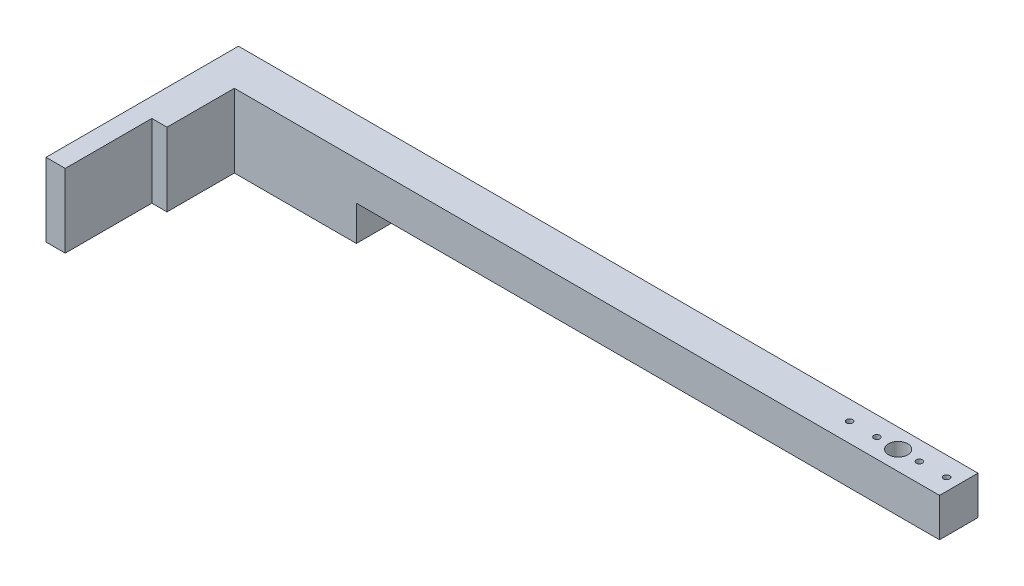
SolidWorks part; units mm, degrees
ref_plane "Front Plane" through (0, 0, 0) normal (0, 0, 1) x (1, 0, 0)
ref_plane "Top Plane" through (0, 0, 0) normal (0, 1, 0) x (1, 0, 0)
ref_plane "Right Plane" through (0, 0, 0) normal (1, 0, 0) x (0, 0, -1)
sketch "Sketch1" plane through (0, 0, 0) normal (0, 1, 0) x (1, 0, 0)
  circle A3 centre (0, -38.254) radius 38.254 construction
  circle A4 centre (0, -40.254) radius 40.254 construction
  circle A5 centre (0, -45.254) radius 45.254 construction
  dimension "D1" = 90.508
  dimension "D2" = 80.508
  dimension "D3" = 76.508
sketch "Sketch3" plane through (0, 0, 0) normal (0, 1, 0) x (1, 0, 0)
  line L0 (0, 0) -> (-40.254, 0)
  line L1 (-40.254, 0) -> (-40.254, -22.225)
  line L2 (-45.254, -22.225) -> (-45.254, -50.8)
  line L3 (-40.254, -22.225) -> (-45.254, -22.225)
  line L4 (-45.254, -50.8) -> (-51.604, -50.8)
  line L5 (-51.604, -50.8) -> (-51.604, 12.7)
  line L6 (-51.604, 12.7) -> (0, 12.7)
  line L7 (0, 12.7) -> (0, 0)
  circle A0 centre (0, -40.254) radius 40.254 construction
  circle A1 centre (0, -45.254) radius 45.254 construction
  dimension "D1" = 22.225
  dimension "D2" = 50.8
  dimension "D3" = 6.35
  dimension "D4" = 12.7
extrude "Boss-Extrude1" add sketch "Sketch3" along normal blind 12.7 and the other way blind 11.525
sketch "Sketch5" plane through (0, 0, 0) normal (1, 0, 0) x (0, 0, -1)
  line L0 (12.7, -11.525) -> (12.7, 12.7) construction
  line L1 (0, 0) -> (12.7, 0)
  line L2 (0, 0) -> (0, 12.7)
  line L3 (0, 12.7) -> (12.7, 12.7)
  line L4 (12.7, 0) -> (12.7, 12.7)
extrude "Boss-Extrude2" add sketch "Sketch5" along normal blind 152.4
sketch "Sketch8" plane through (0, 12.7, 0) normal (0, 1, 0) x (1, 0, 0)
  line L0 (-40.254, 0) -> (152.4, 0) construction
  line L1 (152.4, 12.7) -> (192.4, 12.7)
  line L2 (152.4, 12.7) -> (152.4, 0)
  line L3 (152.4, 0) -> (192.4, 0)
  line L4 (152.4, 12.7) -> (152.4, 0) construction
  line L5 (192.4, 12.7) -> (192.4, 0)
  line L6 (172.4, 12.7) -> (172.4, 0) construction
  circle A0 centre (156.4, 6.35) radius 1
  circle A1 centre (165.4, 6.35) radius 1
  circle A4 centre (172.4, 6.35) radius 3.175
  circle A5 centre (188.4, 6.35) radius 1
  circle A6 centre (179.4, 6.35) radius 1
  point P4 (0, 0)
  point P9 (152.4, 6.35)
  dimension "D1" = 2
  dimension "D4" = 6.35
  dimension "D2" = 40
  dimension "D3" = 7
  dimension "D5" = 16
extrude "Boss-Extrude3" add sketch "Sketch8" against normal blind 12.7
equation "\"tightTol\"= 0.005in"
equation "\"normTol\"= 0.01in"
equation "\"looseTol\"= 0.02in"
equation "\"D1@Sketch1\"=\"looseTol\"+9cm"
equation "\"D2@Sketch1\"=8cm+\"looseTol\""
equation "\"D3@Sketch1\"=7.6cm+\"looseTol\""
equation "\"D2@Boss-Extrude1\"=0.875-10.7mm"
equation "\"D1@Sketch8\"= 2mm"
equation "\"D2@Sketch8\"=40mm"
equation "\"D3@Sketch8\"=7mm"
equation "\"D5@Sketch8\"=16mm"
